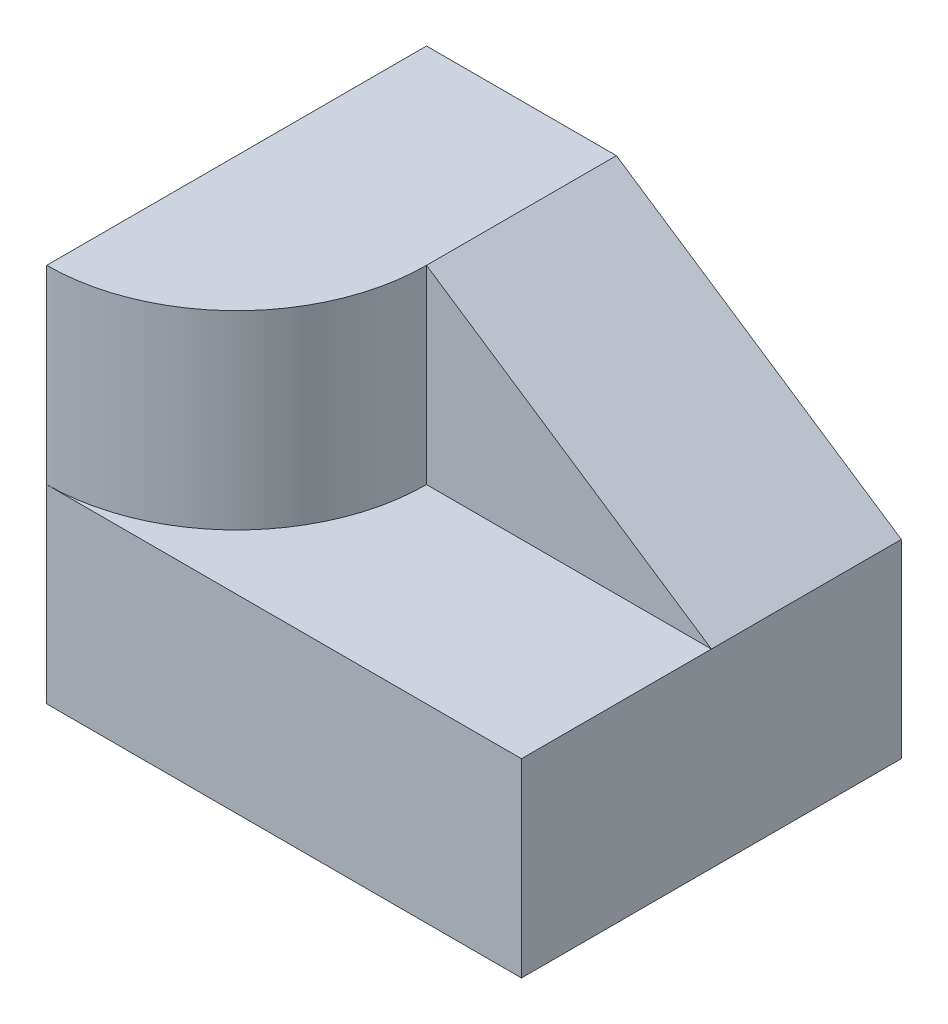
SolidWorks part; units mm, degrees
ref_plane "前基準面" through (0, 0, 0) normal (0, 0, 1) x (1, 0, 0)
ref_plane "上基準面" through (0, 0, 0) normal (0, 1, 0) x (1, 0, 0)
ref_plane "右基準面" through (0, 0, 0) normal (1, 0, 0) x (0, 0, -1)
sketch "草圖1" plane through (0, 0, 0) normal (0, 1, 0) x (1, 0, 0)
  line L1 (-12.5, -10) -> (12.5, -10)
  line L2 (-12.5, -10) -> (-12.5, 10)
  line L3 (-12.5, 10) -> (12.5, 10)
  line L4 (12.5, -10) -> (12.5, 10)
  line L5 (-12.5, -10) -> (12.5, 10) construction
  line L6 (-12.5, 10) -> (12.5, -10) construction
  line L7 (-12.5, 10) -> (-2.5, 10)
  line L8 (-12.5, 10) -> (-12.5, -10)
  line L9 (-12.5, -10) -> (-2.5, -10)
  line L10 (-2.5, 10) -> (-2.5, 0)
  line L11 (12.5, 10) -> (-2.5, 10)
  line L12 (12.5, 10) -> (12.5, 0)
  line L13 (12.5, 0) -> (-2.5, 0)
  line L14 (-2.5, 10) -> (-2.5, 0)
  arc A0 (-2.5, 0) -> (-12.5, -10) centre (-12.5, 0) cw
  point P0 (0, 0)
  dimension "D1" = 20
  dimension "D2" = 25
  dimension "D3" = 10
  dimension "D4" = 10
extrude "填料-伸長1" add sketch "草圖1" along normal blind 10 contours A0 L10 L3 L2 | L13 A0 L1 L4 | L13 L4 L3 L10 region at (3.7817, 0, 5.3462) region at (-7.8325, 0, -0.9335) region at (5, 0, -5)
extrude "填料-伸長2" add sketch "草圖1<3>" along normal blind 20 contours A0 L10 L3 L2 | L13 L4 L3 L10 region at (-7.8325, 0, -0.9335) region at (5, 0, -5)
sketch "草圖1<3>" plane through (0, 0, 0) normal (0, 1, 0) x (1, 0, 0) same geometry as "草圖1"
sketch "草圖2" plane through (0, 0, 0) normal (0, 0, 1) x (1, 0, 0)
  line L0 (-2.5, 20) -> (12.5, 10)
  line L1 (12.5, 10) -> (12.5, 20)
  line L2 (12.5, 20) -> (-2.5, 20)
extrude "除料-伸長1" cut sketch "草圖2" against normal blind 20
